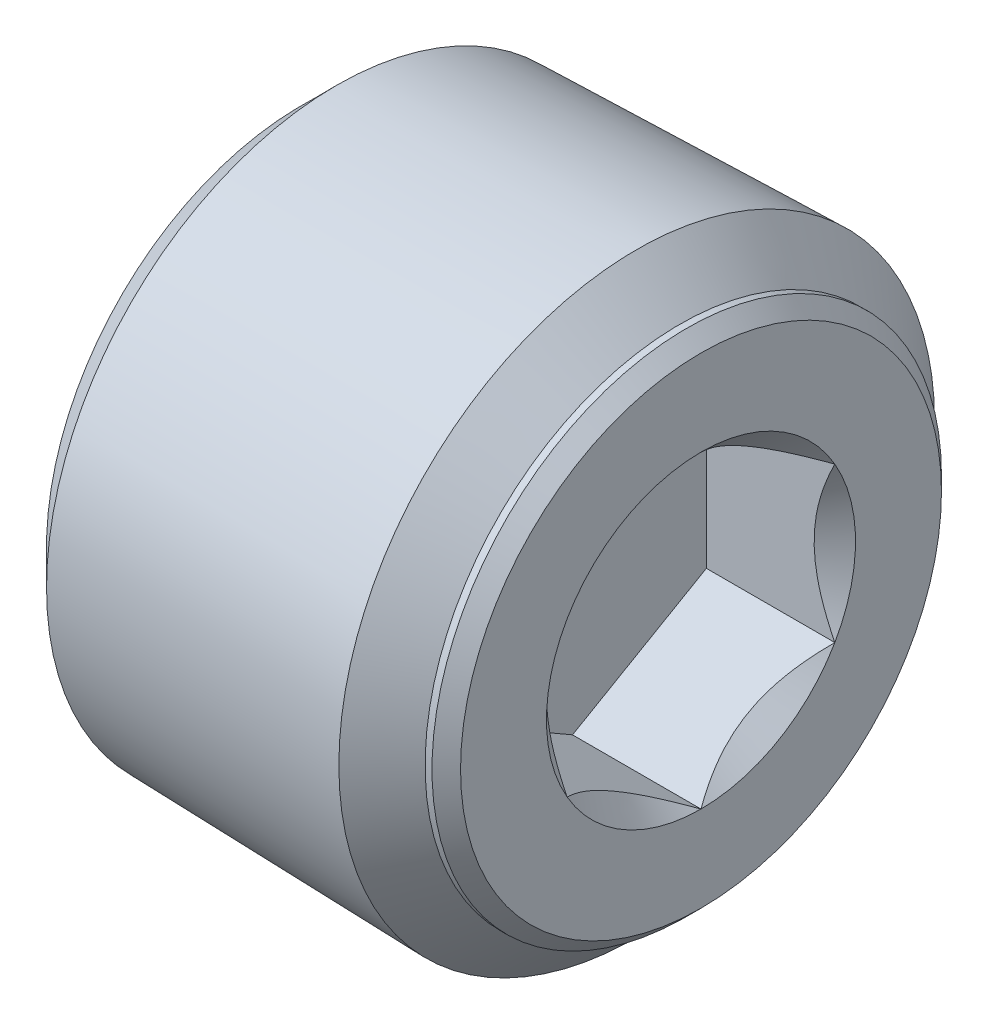
SolidWorks part; units mm, degrees
material "Alloy Steel (SS)"
ref_plane "Front" through (0, 0, 0) normal (0, 0, 1) x (1, 0, 0)
ref_plane "Top" through (0, 0, 0) normal (0, 1, 0) x (1, 0, 0)
ref_plane "Right" through (0, 0, 0) normal (1, 0, 0) x (0, 0, -1)
sketch "Sketch1" plane through (0, 0, 0) normal (0, 0, 1) x (1, 0, 0)
  line L0 (-3.556, 0) -> (3.556, 0) construction
ref_plane "Plane1" through (-3.556, 0, 0) normal (1, 0, 0) x (0, 0, -1)
sketch "Sketch2" plane through (-3.556, 0, 0) normal (1, 0, 0) x (0, 0, -1)
  circle A0 centre (0, 0) radius 5.1435
  dimension "OD" = 10.287
extrude "Extrude1" add sketch "Sketch2" along normal up to vertex (7.112 mm away) draft 1.5 up to point (3.556, 0, 0) draft outward yes
sketch "Sketch3" plane through (-3.556, 0, 0) normal (-1, 0, 0) x (0, 0, 1)
  circle A1 centre (0, 0) radius 5.1435
  circle A2 centre (0, 0) radius 5.1435
  dimension "D1" = 0
curve "Helix/Spiral1" [suppressed] parameters "pitch"=0.9407
sketch "Sketch4" plane through (0, 0, 0) normal (0, 0, 1) x (1, 0, 0)
  line L0 (-4.3791, 5.1435) -> (-4.0264, 4.5325)
  line L1 (-4.0264, 4.5325) -> (-3.9088, 4.5325)
  line L2 (-3.9088, 4.5325) -> (-3.556, 5.1435)
  line L3 (-4.3791, 5.1435) -> (-3.556, 5.1435) construction
  line L4 (-4.2028, 4.838) -> (-3.7324, 4.838) construction
  line L5 (-3.9676, 4.5325) -> (-3.9676, 5.1435) construction
  line L6 (-4.3791, 5.1435) -> (-3.4627, 5.3051)
  line L7 (-3.556, 5.1435) -> (-3.4627, 5.3051)
  line L8 (-3.556, 5.1435) -> (-3.556, -5.1435) construction
  dimension "D1" = 10
  dimension "D2" = 0.1176
  dimension "D3" = 0.4704
  dimension "D4" = 60
sweep "Cut-Sweep1" [suppressed] cut profiles "Sketch4" path "Helix/Spiral1"
sketch "Sketch5" plane through (-3.556, 0, 0) normal (1, 0, 0) x (0, 0, -1)
  circle A0 centre (0, 0) radius 4.5325
extrude "Cut-Extrude1" cut sketch "Sketch5" along normal through all draft 45 flip side to cut
ref_plane "Plane2" through (3.556, 0, 0) normal (1, 0, 0) x (0, 0, -1)
ref_plane "Plane3" through (-3.8354, 0, 0) normal (1, 0, 0) x (0, 0, -1)
sketch "Sketch9" plane through (3.556, 0, 0) normal (1, 0, 0) x (0, 0, -1)
  circle A0 centre (0, 0) radius 5.1435 construction
  circle A2 centre (0, 0) radius 4.5325
extrude "Cut-Extrude5" cut sketch "Sketch9" against normal blind 0.3763 flip side to cut
ref_plane "Plane4" through (3.1797, 0, 0) normal (1, 0, 0) x (0, 0, -1)
sketch "Sketch10" plane through (3.1797, 0, 0) normal (1, 0, 0) x (0, 0, -1)
  circle A1 centre (0, 0) radius 4.5325
  circle A2 centre (0, 0) radius 4.5325
  dimension "D1" = 0
extrude "Cut-Extrude6" cut sketch "Sketch10" against normal through all draft 45 flip side to cut
sketch "Sketch6" plane through (3.556, 0, 0) normal (1, 0, 0) x (0, 0, -1)
  line L1 (0, 2.7496) -> (-2.3813, 1.3748)
  line L2 (-2.3813, 1.3748) -> (-2.3813, -1.3748)
  line L3 (-2.3813, -1.3748) -> (0, -2.7496)
  line L4 (0, -2.7496) -> (2.3813, -1.3748)
  line L5 (2.3813, -1.3748) -> (2.3813, 1.3748)
  line L6 (2.3813, 1.3748) -> (0, 2.7496)
  circle A0 centre (0, 0) radius 2.3813 construction
  dimension "Hex" = 4.7625
extrude "Cut-Extrude7" cut sketch "Sketch6" against normal blind 2.286
chamfer "Chamfer1" distance 0.254 angle 45 1 edges at (3.556, 0, -4.5325)
sketch "Sketch11" plane through (3.556, 0, 0) normal (1, 0, 0) x (0, 0, -1)
  circle A0 centre (0, 0) radius 2.7496
extrude "Cut-Extrude8" cut sketch "Sketch11" against normal blind 2.286 draft 45
equation "\"D3@Helix/Spiral1\" = \"L@Sketch1\""
equation "\"D2@Sketch4\" = \"pitch@Helix/Spiral1\"*.125"
equation "\"D3@Sketch4\" = \"pitch@Helix/Spiral1\"*.5"
equation "\"D1@Cut-Extrude5\" = \"pitch@Helix/Spiral1\"*.4"
equation "\"D1@Plane4\" = \"D1@Cut-Extrude5\""
equation "\"D1@Cut-Extrude8\" = \"D1@Cut-Extrude7\""
